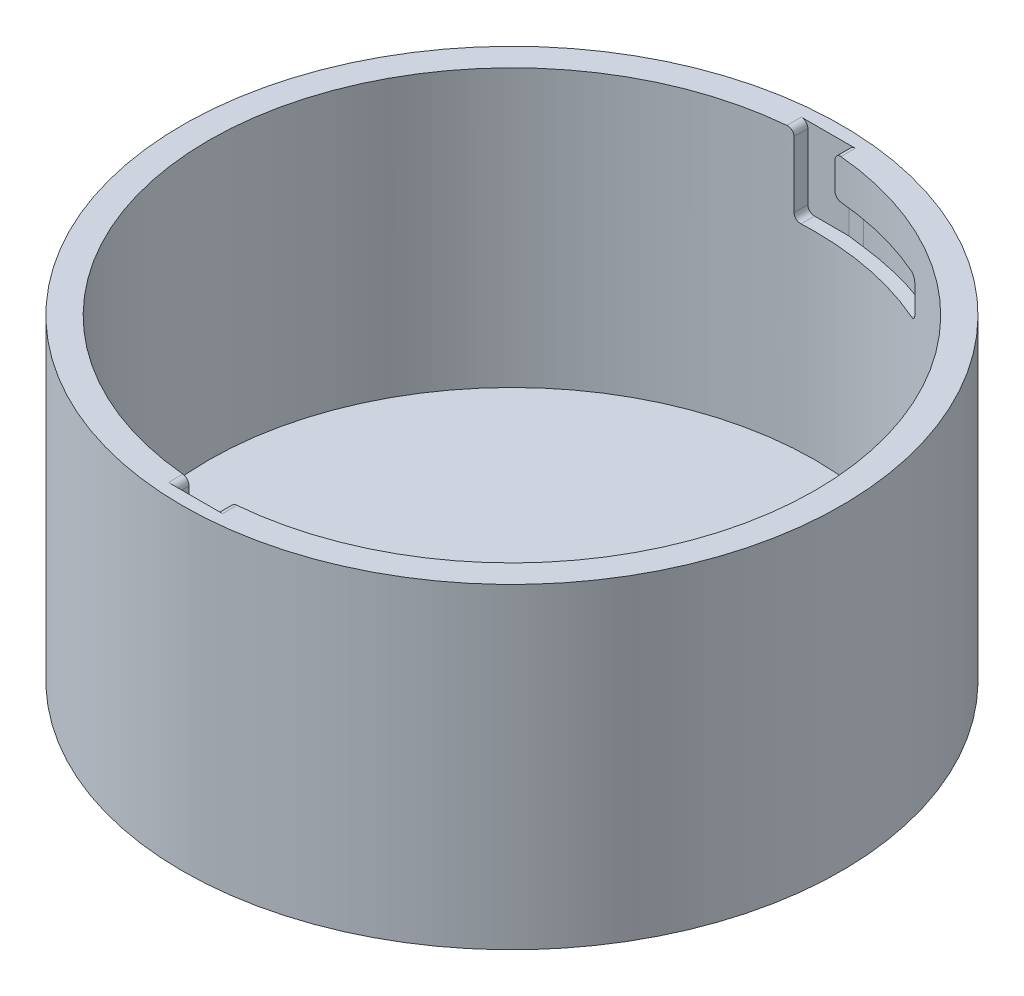
SolidWorks part; units mm, degrees
ref_plane "Front Plane" through (0, 0, 0) normal (0, 0, 1) x (1, 0, 0)
ref_plane "Top Plane" through (0, 0, 0) normal (0, 1, 0) x (1, 0, 0)
ref_plane "Right Plane" through (0, 0, 0) normal (1, 0, 0) x (0, 0, -1)
sketch "Sketch2" plane through (0, 0, 0) normal (0, 1, 0) x (1, 0, 0)
  circle A0 centre (0, 0) radius 23
  circle A1 centre (0, 0) radius 25
  dimension "D1" = 50
  dimension "D2" = 2
extrude "Boss-Extrude1" add sketch "Sketch2" along normal blind 24
sketch "Sketch4" plane through (0, 0, 0) normal (0, -1, 0) x (1, 0, 0)
  circle A0 centre (0, 0) radius 25
  point P3 (0, 0)
  dimension "D1" = 50
extrude "Boss-Extrude2" add sketch "Sketch4" against normal blind 3
sketch "Sketch5" plane through (0, 24, 0) normal (0, 1, 0) x (1, 0, 0)
  line L0 (-1.55, 12.1669) -> (-1.55, 24)
  line L1 (-1.55, 24) -> (1.55, 24)
  line L2 (1.55, 24) -> (1.55, 12.1669)
  line L3 (-1.55, 12.1669) -> (1.55, 12.1669)
  line L4 (0, 12.1669) -> (0, 0) construction
  line L5 (0, 23) -> (0, 24) construction
  line L6 (-1.9793, 0) -> (2.4501, 0)
  line L7 (-1.55, -12.1669) -> (1.55, -12.1669)
  line L8 (1.55, -24) -> (1.55, -12.1669)
  line L9 (-1.55, -24) -> (1.55, -24)
  line L10 (-1.55, -12.1669) -> (-1.55, -24)
  circle A0 centre (0, 0) radius 23 construction
  circle A1 centre (0, 0) radius 23 construction
  circle M9 centre (0, 0) radius 23
  dimension "D1" = 3.1
  dimension "D2" = 1
extrude "Cut-Extrude1" cut sketch "Sketch5" against normal blind 6 contours L0 L3 L2 M9 | L2 L1 L0 M9 | L10 L9 L8 M9 | L7 L10 L8 M9 region at (0, 24, -17.5747) region at (0, 24, -23.4912) region at (0, 24, 23.4912) region at (0, 24, 17.5747)
sketch "Sketch6" plane through (0, 0, 0) normal (1, 0, 0) x (0, 0, -1)
  line L0 (22.9477, 24) -> (22.9477, 18) construction
  line L1 (24, 18) -> (22.9477, 18)
  line L2 (24, 18) -> (24, 21)
  line L3 (24, 21) -> (22.9477, 21)
  line L4 (22.9477, 18) -> (22.9477, 21)
  line L5 (-24, 18) -> (-24, 24) construction
  line L6 (-22.9477, 18) -> (-24, 18)
  line L7 (-22.9477, 18) -> (-22.9477, 21)
  line L8 (-22.9477, 21) -> (-24, 21)
  line L9 (-24, 18) -> (-24, 21)
  dimension "D1" = 3
ref_axis "Axis2" through (0, 25.2, 0) along (0, -1, 0)
revolve "Cut-Revolve3" cut sketch "Sketch6" angle 25 about axis through (0, 25.2, 0) along (0, -1, 0)
fillet "Fillet1" radius 0.5 12 edges at (-1.55, 24, -23.4739) (1.55, 24, -23.4739) (-1.55, 18, -23.4739) (1.55, 21, -23.4488) (-9.9315, 18, 21.2982) (-1.55, 21, 23.4488) (-1.55, 24, 23.4739) (1.55, 24, 23.4739) (1.55, 18, 23.4739) (9.9315, 18, -21.2982) (9.9315, 21, -21.2982) (-9.9315, 21, 21.2982)
fillet "Fillet2" radius 50.5 2 edges at (-1.55, 19.75, 23.9499) (1.55, 19.75, -23.9499)
